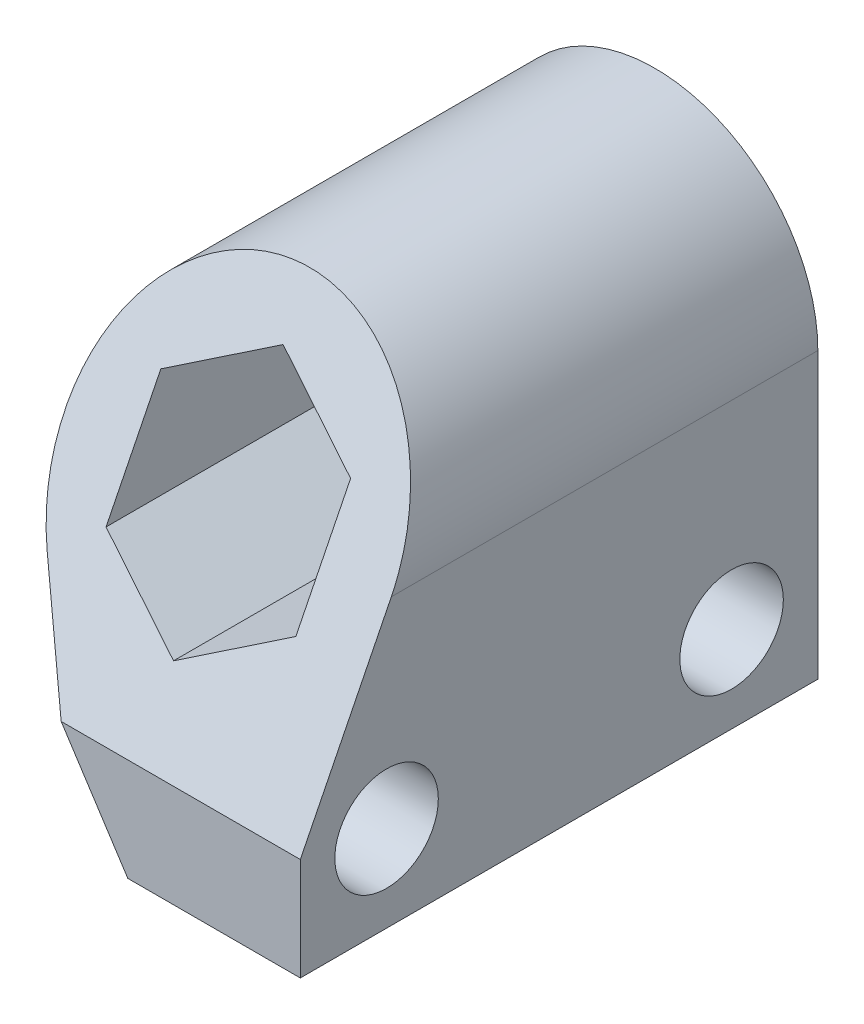
SolidWorks part; units mm, degrees
ref_plane "Front Plane" through (0, 0, 0) normal (0, 0, 1) x (1, 0, 0)
ref_plane "Top Plane" through (0, 0, 0) normal (0, 1, 0) x (1, 0, 0)
ref_plane "Right Plane" through (0, 0, 0) normal (1, 0, 0) x (0, 0, -1)
sketch "Sketch1" plane through (0, 0, 0) normal (0, 0, 1) x (1, 0, 0)
  line L0 (6, 0) -> (6, -10.4775)
  line L1 (3.4925, -2.0164) -> (3.4925, 2.0164)
  line L2 (3.4925, 2.0164) -> (0, 4.0328)
  line L3 (0, 4.0328) -> (-3.4925, 2.0164)
  line L4 (-3.4925, 2.0164) -> (-3.4925, -2.0164)
  line L5 (-3.4925, -2.0164) -> (0, -4.0328)
  line L6 (0, -4.0328) -> (3.4925, -2.0164)
  line L7 (6, -10.4775) -> (-0.35, -10.4775)
  line L8 (-0.35, -10.4775) -> (-5.032, -3.2678)
  line L9 (6, 6.35) -> (6, -29.9338) construction
  circle A0 centre (0, 0) radius 3.4925 construction
  arc A1 (6, 0) -> (-5.032, -3.2678) centre (0, 0) ccw
  point P10 (6.2393, 0)
  point P16 (0, 0)
  dimension "D2" = 6.35
  dimension "D1" = 6.985
  dimension "D3" = 10.4775
extrude "Boss-Extrude1" add sketch "Sketch1" along normal mid plane 19.05
sketch "Sketch2" plane through (6, 0, 0) normal (1, 0, 0) x (0, 0, -1)
  line L0 (-3.175, 6) -> (-9.525, -6.7)
  line L1 (9.525, 6) -> (-9.525, 6) construction
  line L2 (-9.525, -10.4775) -> (-9.525, 0) construction
  line L3 (-9.525, -6.7) -> (-9.525, 6)
  line L4 (-9.525, 6) -> (-3.175, 6)
  dimension "D1" = 6.35
  dimension "D2" = 12.7
extrude "Cut-Extrude1" cut sketch "Sketch2" against normal through all
sketch "Sketch3" plane through (6, 0, 0) normal (1, 0, 0) x (0, 0, -1)
  line L0 (-9.525, -7.3025) -> (-6.35, -7.3025) construction
  line L1 (-9.525, -10.4775) -> (-9.525, -6.7) construction
  line L2 (6.35, -7.3025) -> (9.525, -7.3025) construction
  line L3 (9.525, -10.4775) -> (9.525, 0) construction
  line L4 (-9.525, -10.4775) -> (9.525, -10.4775) construction
  circle A0 centre (-6.35, -7.3025) radius 1.905
  circle A1 centre (6.35, -7.3025) radius 1.905
  dimension "D1" = 3.81
  dimension "D2" = 12.7
  dimension "D3" = 3.175
extrude "Cut-Extrude2" cut sketch "Sketch3" against normal through all
